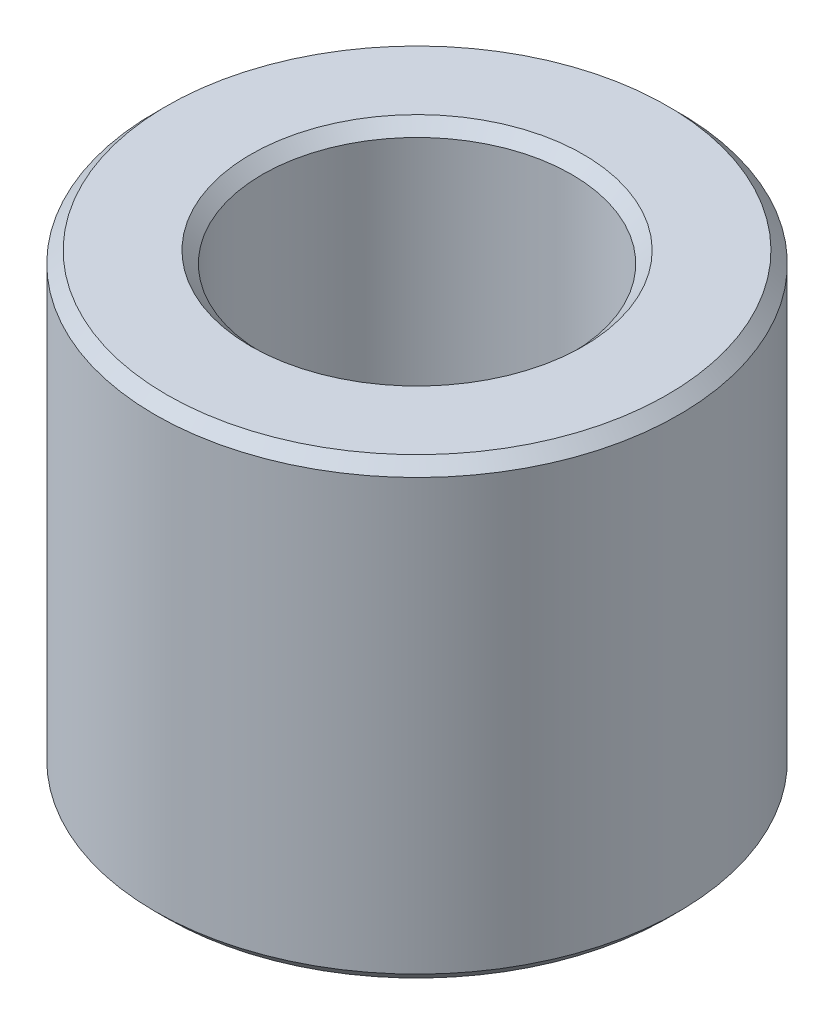
SolidWorks part; units mm, degrees
ref_plane "Front Plane" through (0, 0, 0) normal (0, 0, 1) x (1, 0, 0)
ref_plane "Top Plane" through (0, 0, 0) normal (0, 1, 0) x (1, 0, 0)
ref_plane "Right Plane" through (0, 0, 0) normal (1, 0, 0) x (0, 0, -1)
sketch "Sketch1" plane through (0, 0, 0) normal (0, 1, 0) x (1, 0, 0)
  circle A0 centre (0, 0) radius 32.5
  dimension "SLEEVE_OD" = 65
extrude "Boss-Extrude1" add sketch "Sketch1" along normal blind 56.2595
sketch "Sketch2" plane through (0, 0, 0) normal (0, 1, 0) x (1, 0, 0)
  circle A0 centre (0, 0) radius 19.1952
  dimension "BORE_D" = 38.3904
extrude "Cut-Extrude1" cut sketch "Sketch2" along normal through all
chamfer "Chamfer1" distance 1.4396 angle 45 4 edges at (0, 56.2595, 19.1952) (0, 0, 19.1952) (0, 0, 32.5) (0, 56.2595, 32.5)
